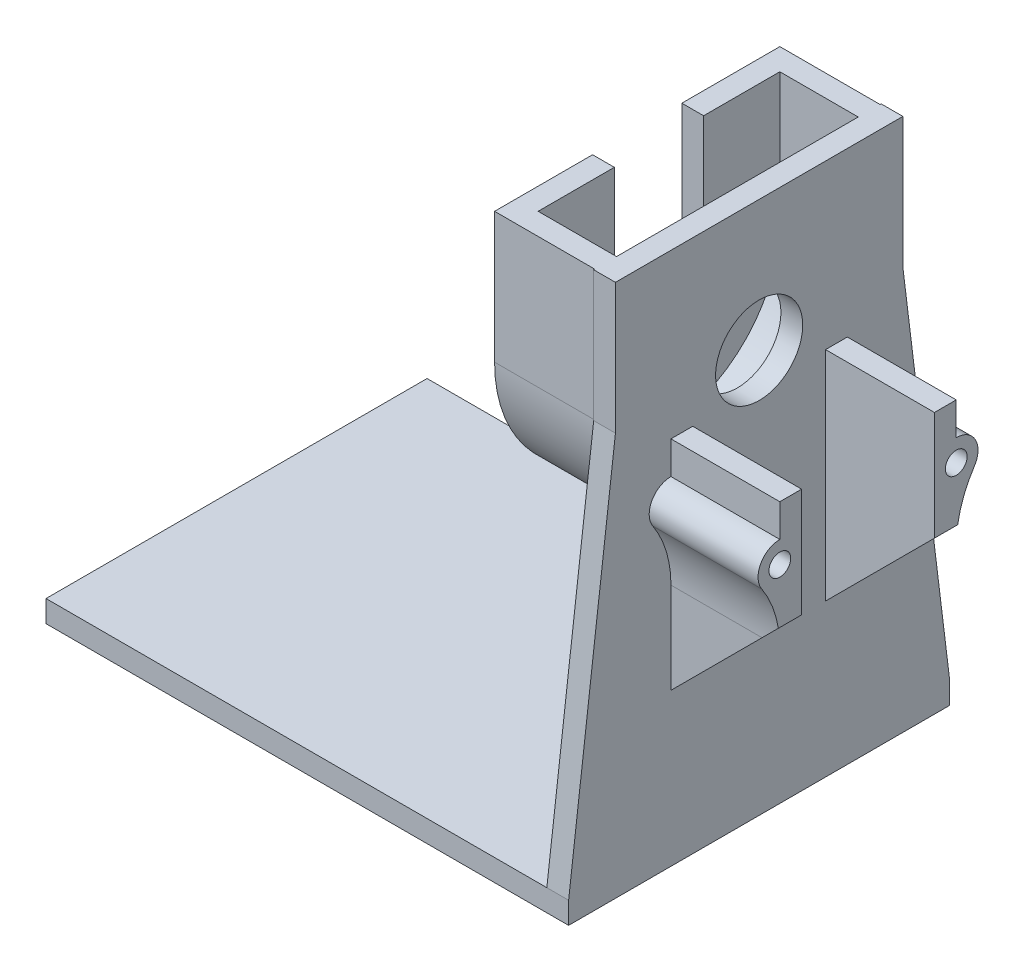
SolidWorks part; units mm, degrees
ref_plane "前视基准面" through (0, 0, 0) normal (0, 0, 1) x (1, 0, 0)
ref_plane "上视基准面" through (0, 0, 0) normal (0, 1, 0) x (1, 0, 0)
ref_plane "右视基准面" through (0, 0, 0) normal (1, 0, 0) x (0, 0, -1)
sketch "草图3" plane through (0, 0, 0) normal (1, 0, 0) x (0, 0, -1)
  circle A0 centre (0, 0) radius 11.1
  circle A1 centre (0, 0) radius 13.1
  dimension "D1" = 22.2
  dimension "D2" = 2
extrude "凸台-拉伸2" add sketch "草图3" along normal blind 7.2
sketch "草图4" plane through (7.2, 0, 0) normal (1, 0, 0) x (0, 0, -1)
  line L0 (13.0022, 1.5979) -> (17.5, -35)
  line L1 (17.5, -35) -> (-17.5, -35)
  line L2 (-17.5, -35) -> (-13.0022, 1.5979)
  line L3 (0, 21.3824) -> (0, -44.3388) construction
  line L4 (13.0022, 1.5979) -> (13.0022, 12)
  line L5 (13.0022, 12) -> (-13.0022, 12)
  line L6 (-13.0022, 1.5979) -> (-13.0022, 12)
  circle A2 centre (0, 0) radius 7.5 construction
  point P11 (0, 12)
  point P21 (0, 0)
  dimension "D4" = 12
  dimension "D5" = 15
  dimension "D2" = 35
  dimension "D3" = 35
extrude "凸台-拉伸3" add sketch "草图4" along normal blind 2
sketch "草图6" plane through (0, -35, 0) normal (0, -1, 0) x (-1, 0, 0)
  line L0 (-9.2, 17.5) -> (-7.2, 17.5) construction
  line L1 (-9.2, -17.5) -> (38.8, -17.5)
  line L2 (-9.2, -17.5) -> (-9.2, 17.5)
  line L3 (-9.2, 17.5) -> (38.8, 17.5)
  line L4 (38.8, -17.5) -> (38.8, 17.5)
  dimension "D1" = 48
extrude "凸台-拉伸7" add sketch "草图6" along normal blind 2
ref_plane "基准面4" through (-14.8, 0, 0) normal (1, 0, 0) x (0, 0, -1)
sketch "草图8" plane through (-38.8, 0, 0) normal (-1, 0, 0) x (0, 0, 1)
  line L0 (-15.6207, 0) -> (15.4278, 0)
  line L1 (15.4278, 0) -> (15.4278, 16.803)
  line L2 (15.4278, 16.803) -> (-15.6207, 16.803)
  line L3 (-15.6207, 16.803) -> (-15.6207, 0)
extrude "切除-拉伸1" cut sketch "草图8" against normal through all
sketch "草图16" plane through (0, 0, 0) normal (0, 1, 0) x (1, 0, 0)
  line L12 (9.2, -13.1986) -> (9.2, 13.1986)
  line L13 (9.2, 13.1986) -> (7.2, 13.1986)
  line L14 (7.2, 13.1986) -> (7.2, 13.1)
  line L15 (7.2, 13.1) -> (0, 13.1)
  line L16 (0, 13.1) -> (0, 11.1)
  line L17 (0, 11.1) -> (7.2, 11.1)
  line L18 (7.2, 11.1) -> (7.2, -11.1)
  line L19 (7.2, -11.1) -> (0, -11.1)
  line L20 (0, -11.1) -> (0, -13.1)
  line L21 (0, -13.1) -> (7.2, -13.1)
  line L22 (7.2, -13.1) -> (7.2, -13.1986)
  line L23 (7.2, -13.1986) -> (9.2, -13.1986)
  line L24 (9.2, -13.1986) -> (9.2, 13.1986)
  line L25 (9.2, 13.1986) -> (7.2, 13.1986)
  line L26 (7.2, 13.1986) -> (7.2, 13.1)
  line L27 (7.2, 13.1) -> (0, 13.1)
  line L28 (0, 13.1) -> (0, 11.1)
  line L29 (0, 11.1) -> (7.2, 11.1)
  line L30 (7.2, 11.1) -> (7.2, -11.1)
  line L31 (7.2, -11.1) -> (0, -11.1)
  line L32 (0, -11.1) -> (0, -13.1)
  line L33 (0, -13.1) -> (7.2, -13.1)
  line L34 (7.2, -13.1) -> (7.2, -13.1986)
  line L35 (7.2, -13.1986) -> (9.2, -13.1986)
  dimension "D1" = 0
extrude "凸台-拉伸15" add sketch "草图16" along normal blind 12
sketch "草图12" plane through (0, 0, 0) normal (-1, 0, 0) x (0, 0, 1)
  line L0 (-13.1, 0) -> (-13.1, 12)
  line L1 (13.1, 0) -> (13.1, 12)
  line L2 (-13.1, 12) -> (-4.1, 12)
  line L3 (-4.1, 0) -> (-4.1, 12)
  line L4 (4.1, 0) -> (4.1, 12)
  line L5 (4.1, 12) -> (13.1, 12)
  arc A0 (-13.1, 0) -> (13.1, 0) centre (0, 0) ccw
  arc A1 (-4.1, 0) -> (4.1, 0) centre (0, 0) ccw
  point P10 (0, 0)
  dimension "D2" = 13.1
  dimension "D1" = 4.1
extrude "凸台-拉伸12" add sketch "草图12" along normal blind 2
sketch "草图5" plane through (0, 0, 0) normal (0, 0, 1) x (1, 0, 0)
  line L0 (7.2, -35) -> (-0.5, -35)
  line L1 (-0.5, -35) -> (-0.5, -12.2467)
  line L2 (-2, 0) -> (-2, -13.1) construction
  line L3 (-0.5, -12.2467) -> (7.2, -12.2467)
  line L4 (7.2, -12.2467) -> (7.2, -35)
  line L6 (7.2, 0) -> (7.2, -13.1) construction
  dimension "D1" = 1.5
extrude "凸台-拉伸6" add sketch "草图5" along normal mid plane 3
sketch "草图17" plane through (9.2, 0, 0) normal (1, 0, 0) x (0, 0, -1)
  line L0 (0, 24.0178) -> (0, -56.0887) construction
  line L1 (6.1, -3) -> (6.1, -13)
  line L2 (6.1, -13) -> (8.1, -13)
  line L3 (8.1, -13) -> (8.1, -10)
  line L4 (8.1, -3) -> (6.1, -3)
  line L5 (8.1, -6) -> (8.1, -3)
  line L6 (-8.1, -6) -> (-8.1, -3)
  line L7 (-8.1, -3) -> (-6.1, -3)
  line L8 (-8.1, -13) -> (-8.1, -10)
  line L9 (-6.1, -13) -> (-8.1, -13)
  line L10 (-6.1, -3) -> (-6.1, -13)
  arc A0 (8.1, -10) -> (8.1, -6) centre (8.1, -8) ccw
  circle A1 centre (8.1, -8) radius 1
  circle A2 centre (-8.1, -8) radius 1
  arc A3 (-8.1, -10) -> (-8.1, -6) centre (-8.1, -8) cw
  point P18 (6.1, -8)
  point P19 (0, -3)
  dimension "D3" = 2
  dimension "D5" = 2
  dimension "D1" = 2
  dimension "D2" = 10
  dimension "D4" = 2
  dimension "D6" = 12.2
  dimension "D7" = 3
extrude "凸台-拉伸16" add sketch "草图17" along normal blind 10
sketch "草图18" plane through (9.2, 0, 0) normal (1, 0, 0) x (0, 0, -1)
  circle A0 centre (0, 0) radius 4
  dimension "D1" = 8
extrude "切除-拉伸2" cut sketch "草图18" against normal blind 10
chamfer "倒角1" distance 10 angle 45 2 edges at (9.2, -13, -7.1) (9.2, -13, 7.1)
fillet "圆角1" radius 10 2 edges at (14.2, -10, -8.1) (14.2, -10, 8.1)
fillet "圆角2" radius 15 2 edges at (3.35, -13.0138, -1.5) (3.35, -13.0138, 1.5)
fillet "圆角3" radius 15 1 edges at (-0.5, -13.1, 0)
